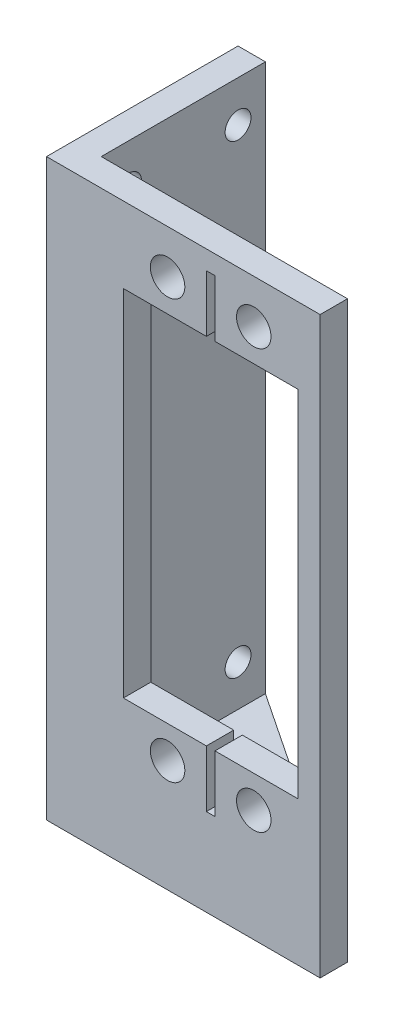
SolidWorks part; units mm, degrees
ref_plane "Front Plane" through (0, 0, 0) normal (0, 0, 1) x (1, 0, 0)
ref_plane "Top Plane" through (0, 0, 0) normal (0, 1, 0) x (1, 0, 0)
ref_plane "Right Plane" through (0, 0, 0) normal (1, 0, 0) x (0, 0, -1)
sketch "Sketch2" plane through (0, 0, 0) normal (0, 0, 1) x (1, 0, 0)
  line L1 (0, 0) -> (31.75, 0)
  line L2 (0, 0) -> (0, 63.5)
  line L3 (0, 63.5) -> (31.75, 63.5)
  line L4 (31.75, 0) -> (31.75, 63.5)
  dimension "D1" = 63.5
  dimension "D2" = 31.75
extrude "Boss-Extrude1" add sketch "Sketch2" along normal blind 3.175 contours L4 L3 L2 L1
sketch "Sketch3" plane through (0, 0, 3.175) normal (0, 0, 1) x (1, 0, 0)
  line L0 (8.923, 54.704) -> (29.177, 13.55) construction
  line L1 (8.923, 54.704) -> (18.55, 54.704)
  line L2 (8.923, 54.704) -> (8.923, 13.55)
  line L3 (8.923, 13.55) -> (18.55, 13.55)
  line L4 (29.177, 54.704) -> (29.177, 13.55)
  line L5 (29.177, 54.704) -> (8.923, 13.55) construction
  line L6 (14.05, 58.427) -> (24.05, 9.827) construction
  line L7 (14.05, 9.827) -> (24.05, 58.427) construction
  line L8 (19.55, 13.55) -> (29.177, 13.55)
  line L9 (18.55, 13.55) -> (18.55, 6.946)
  line L10 (18.55, 6.946) -> (19.55, 6.946)
  line L11 (19.55, 13.55) -> (19.55, 6.946)
  line L12 (19.05, 34.127) -> (62.1329, 34.127) construction
  line L13 (18.55, 61.308) -> (19.55, 61.308)
  line L14 (18.55, 54.704) -> (18.55, 61.308)
  line L15 (19.55, 54.704) -> (19.55, 61.308)
  line L16 (19.55, 54.704) -> (29.177, 54.704)
  line L17 (0, 0) -> (0, 63.5) construction
  line L18 (0, 63.5) -> (31.75, 63.5) construction
  circle A0 centre (14.05, 9.827) radius 2
  circle A1 centre (24.05, 9.827) radius 2
  circle A2 centre (14.05, 58.427) radius 2
  circle A3 centre (24.05, 58.427) radius 2
  point P8 (19.05, 6.946)
  point P17 (19.05, 34.127)
  point P18 (19.05, 34.127)
  point P27 (19.05, 44.45)
  dimension "D3" = 4
  dimension "D1" = 10
  dimension "D2" = 48.6
  dimension "D4" = 41.154
  dimension "D5" = 20.254
  dimension "D6" = 1
  dimension "D7" = 6.604
  dimension "D8" = 30.9
  dimension "D9" = 19.05
  dimension "D10" = 19.05
extrude "Cut-Extrude1" cut sketch "Sketch3" against normal through all
sketch "Sketch4" plane through (0, 0, 3.175) normal (0, 0, 1) x (1, 0, 0)
  line L0 (0, 0) -> (31.75, 0) construction
  line L1 (0, 63.5) -> (3.175, 63.5)
  line L2 (0, 63.5) -> (0, 0)
  line L3 (0, 0) -> (3.175, 0)
  line L4 (3.175, 63.5) -> (3.175, 0)
  dimension "D1" = 3.175
extrude "Boss-Extrude2" add sketch "Sketch4" against normal blind 19.05 from surface starting at face at (26.05, 9.827, 0)
sketch "Sketch5" plane through (0, 0, 0) normal (0, -1, 0) x (1, 0, 0)
  line L0 (0, 3.175) -> (31.75, 3.175)
  line L1 (31.75, 3.175) -> (31.75, 0)
  line L2 (31.75, 0) -> (3.175, -19.05)
  line L3 (3.175, -19.05) -> (0, -19.05)
  line L4 (0, -19.05) -> (0, 3.175)
extrude "Boss-Extrude3" add sketch "Sketch5" along normal blind 3.175
sketch "Sketch6" plane through (3.175, 0, 0) normal (1, 0, 0) x (0, 0, -1)
  line L0 (0, 0) -> (0, 63.5) construction
  line L1 (19.05, 0) -> (19.05, 63.5) construction
  line L2 (19.05, 63.5) -> (0, 63.5) construction
  line L4 (19.05, 0) -> (0, 0) construction
  circle A0 centre (3.175, 58.7375) radius 1.5
  circle A1 centre (3.175, 4.7625) radius 1.5
  circle A2 centre (15.875, 58.7375) radius 1.5
  circle A3 centre (15.875, 4.7625) radius 1.5
  dimension "D5" = 3
  dimension "D1" = 3.175
  dimension "D2" = 3.175
  dimension "D3" = 4.7625
  dimension "D4" = 4.7625
extrude "Cut-Extrude2" cut sketch "Sketch6" against normal through all
equation "\"D8@Sketch3\"=30.9mm"
equation "\"tightTol\"= 0.005in"
equation "\"normTol\"= 0.01in"
equation "\"looseTol\"= 0.02in"
equation "\"D5@Sketch6\"=3mm"
